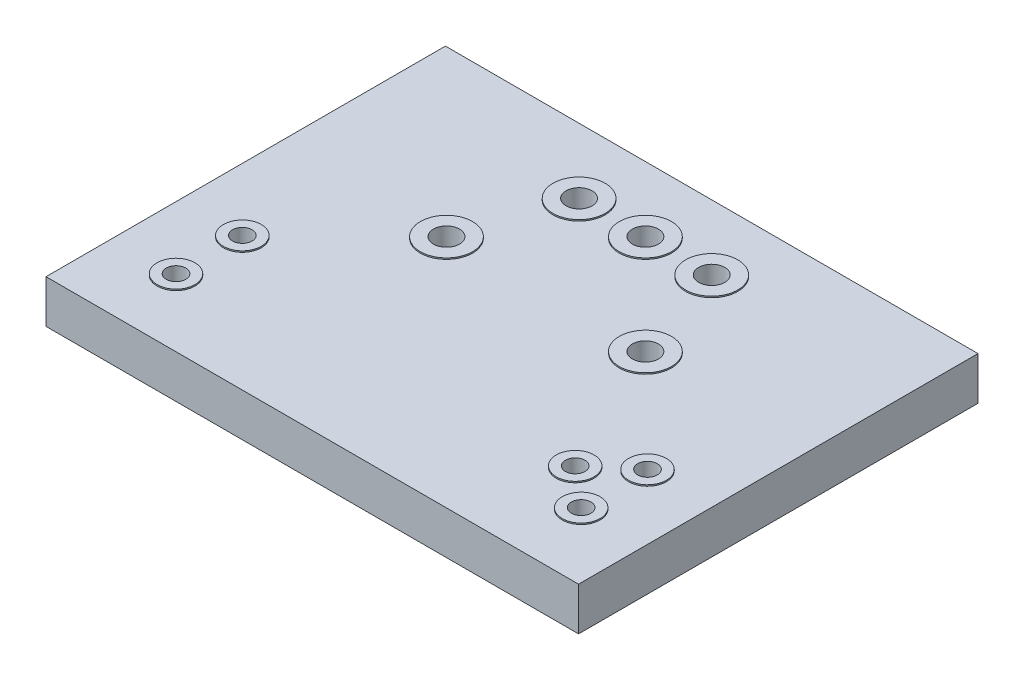
SolidWorks part; units mm, degrees
ref_plane "Front Plane" through (0, 0, 0) normal (0, 0, 1) x (1, 0, 0)
ref_plane "Top Plane" through (0, 0, 0) normal (0, 1, 0) x (1, 0, 0)
ref_plane "Right Plane" through (0, 0, 0) normal (1, 0, 0) x (0, 0, -1)
sketch "Sketch3" plane through (0, 0, 0) normal (0, 1, 0) x (1, 0, 0)
  line L0 (7.76, -2.57) -> (7.76, -5.11) construction
  line L1 (-10.2, 7.65) -> (10.2, 7.65)
  line L2 (-10.2, 7.65) -> (-10.2, -7.65)
  line L3 (-10.2, -7.65) -> (10.2, -7.65)
  line L4 (10.2, 7.65) -> (10.2, -7.65)
  line L5 (-10.2, 7.65) -> (10.2, -7.65) construction
  line L6 (-10.2, -7.65) -> (10.2, 7.65) construction
  line L7 (6.26, -3.84) -> (7.76, -3.84) construction
  line L8 (-7.76, -2.57) -> (-7.76, -5.11) construction
  line L9 (-7.76, -3.84) -> (7.76, -3.84) construction
  line L10 (-2.54, 5.11) -> (2.54, 5.11) construction
  line L11 (-3.81, 1.3) -> (3.81, 1.3) construction
  circle A0 centre (-2.54, 5.11) radius 0.5
  circle A1 centre (0, 5.11) radius 0.5
  circle A2 centre (2.54, 5.11) radius 0.5
  circle A3 centre (-7.76, -2.57) radius 0.375
  circle A4 centre (-7.76, -5.11) radius 0.375
  circle A5 centre (7.76, -2.57) radius 0.375
  circle A6 centre (7.76, -5.11) radius 0.375
  circle A7 centre (6.26, -3.84) radius 0.375
  circle A8 centre (-3.81, 1.3) radius 0.5
  circle A9 centre (3.81, 1.3) radius 0.5
  point P0 (0, 0)
  point P24 (0, -3.84)
  point P27 (2.3426, 0)
  point P28 (0, 1.3)
  dimension "D5" = 0.75
  dimension "D7" = 1
  dimension "D1" = 15.3
  dimension "D2" = 20.4
  dimension "D3" = 1.5
  dimension "D4" = 2.54
  dimension "D6" = 15.52
  dimension "D8" = 2.54
  dimension "D9" = 2.54
  dimension "D10" = 2.54
  dimension "D11" = 7.62
  dimension "D12" = 3.81
extrude "Boss-Extrude2" add sketch "Sketch3" along normal mid plane 1.65
sketch "Sketch5" plane through (0, 0.825, 0) normal (0, 1, 0) x (1, 0, 0)
  circle A4 centre (7.76, -5.11) radius 0.375 construction
  circle A5 centre (6.26, -3.84) radius 0.375 construction
  circle A6 centre (7.76, -2.57) radius 0.375 construction
  circle A7 centre (-7.76, -5.11) radius 0.375 construction
  circle A8 centre (-7.76, -2.57) radius 0.375 construction
  circle A9 centre (-3.81, 1.3) radius 0.5 construction
  circle A10 centre (3.81, 1.3) radius 0.5 construction
  circle A11 centre (2.54, 5.11) radius 0.5 construction
  circle A12 centre (0, 5.11) radius 0.5 construction
  circle A13 centre (-2.54, 5.11) radius 0.5 construction
  circle A14 centre (7.76, -5.11) radius 0.375
  circle A15 centre (6.26, -3.84) radius 0.375
  circle A16 centre (7.76, -2.57) radius 0.375
  circle A17 centre (-7.76, -5.11) radius 0.375
  circle A18 centre (-7.76, -2.57) radius 0.375
  circle A19 centre (-3.81, 1.3) radius 0.5
  circle A20 centre (3.81, 1.3) radius 0.5
  circle A21 centre (2.54, 5.11) radius 0.5
  circle A22 centre (0, 5.11) radius 0.5
  circle A23 centre (-2.54, 5.11) radius 0.5
  circle A24 centre (-2.54, 5.11) radius 1
  circle A25 centre (0, 5.11) radius 1
  circle A26 centre (2.54, 5.11) radius 1
  circle A27 centre (3.81, 1.3) radius 1
  circle A28 centre (-3.81, 1.3) radius 1
  circle A29 centre (-7.76, -2.57) radius 0.725
  circle A30 centre (-7.76, -5.11) radius 0.725
  circle A31 centre (6.26, -3.84) radius 0.725
  circle A32 centre (7.76, -5.11) radius 0.725
  circle A33 centre (7.76, -2.57) radius 0.725
  dimension "D1" = 0.35
  dimension "D2" = 0.5
extrude "Boss-Extrude3" add sketch "Sketch5" along normal blind 0.05
mirror "Mirror1" about plane through (0, 0, 0) normal (0, 1, 0) of "Boss-Extrude3"
ref_point "Point1"
ref_plane "Plane2" through (0, 0, 5.11) normal (0, 0, 1) x (1, 0, 0)
